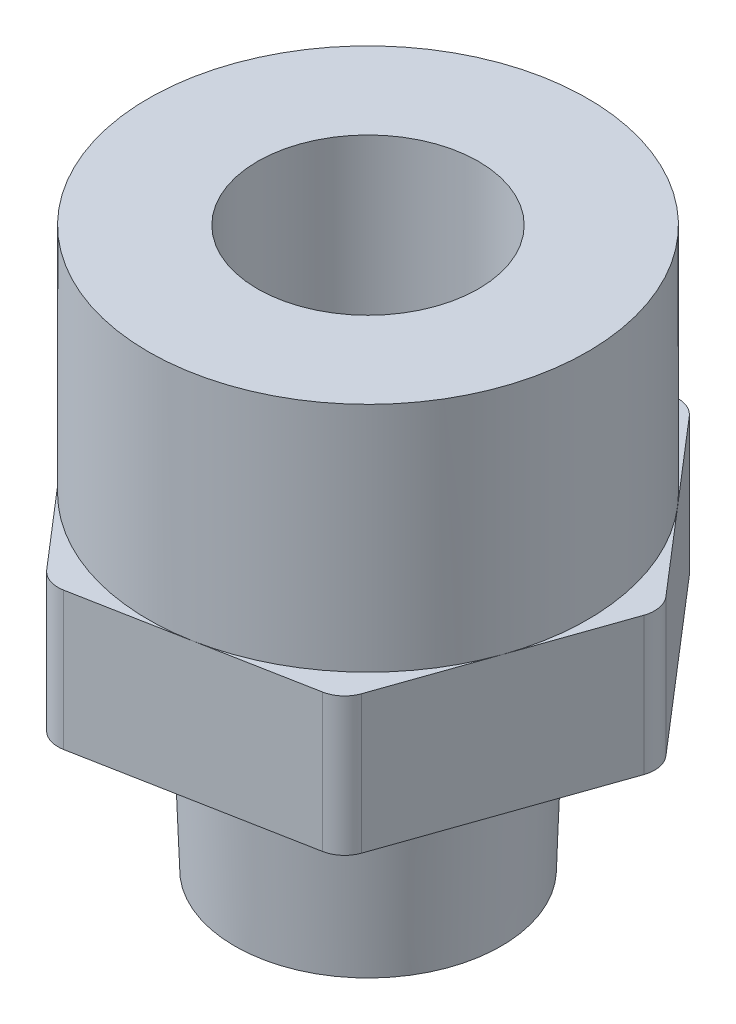
SolidWorks part; units mm, degrees
ref_plane "Front Plane" through (0, 0, 0) normal (0, 0, 1) x (1, 0, 0)
ref_plane "Top Plane" through (0, 0, 0) normal (0, 1, 0) x (1, 0, 0)
ref_plane "Right Plane" through (0, 0, 0) normal (1, 0, 0) x (0, 0, -1)
sketch "Sketch1" plane through (0, 0, 0) normal (0, 1, 0) x (1, 0, 0)
  line L1 (15.2111, -17.672) -> (22.9099, 4.3372)
  line L2 (22.9099, 4.3372) -> (7.6989, 22.0092)
  line L3 (7.6989, 22.0092) -> (-15.2111, 17.672)
  line L4 (-15.2111, 17.672) -> (-22.9099, -4.3372)
  line L5 (-22.9099, -4.3372) -> (-7.6989, -22.0092)
  line L6 (-7.6989, -22.0092) -> (15.2111, -17.672)
  circle A0 centre (0, 0) radius 20.193 construction
  dimension "D1" = 40.386
extrude "Boss-Extrude1" add sketch "Sketch1" along normal blind 12.7
sketch "Sketch2" plane through (0, 12.7, 0) normal (0, 1, 0) x (1, 0, 0)
  circle A0 centre (0, 0) radius 20.193
extrude "Boss-Extrude2" add sketch "Sketch2" along normal blind 21.336
sketch "Sketch3" plane through (0, 0, 0) normal (0, -1, 0) x (1, 0, 0)
  circle A0 centre (0, 0) radius 14.859
  dimension "D1" = 29.718
extrude "Boss-Extrude3" add sketch "Sketch3" along normal blind 4.572
sketch "Sketch4" plane through (0, -4.572, 0) normal (0, -1, 0) x (1, 0, 0)
  circle A0 centre (0, 0) radius 12.7
  dimension "D1" = 25.4
extrude "Boss-Extrude4" add sketch "Sketch4" along normal blind 12.7 draft 2
sketch "Sketch5" plane through (0, -17.272, 0) normal (0, -1, 0) x (1, 0, 0)
  circle A0 centre (0, 0) radius 10.16
  dimension "D1" = 20.32
extrude "Cut-Extrude1" cut sketch "Sketch5" against normal through all
fillet "Fillet1" radius 2.54 7 edges at (0, -4.572, -14.859) (-7.6989, 6.35, 22.0092) (15.2111, 6.35, 17.672) (22.9099, 6.35, -4.3372) (7.6989, 6.35, -22.0092) (-15.2111, 6.35, -17.672) (-22.9099, 6.35, 4.3372)
